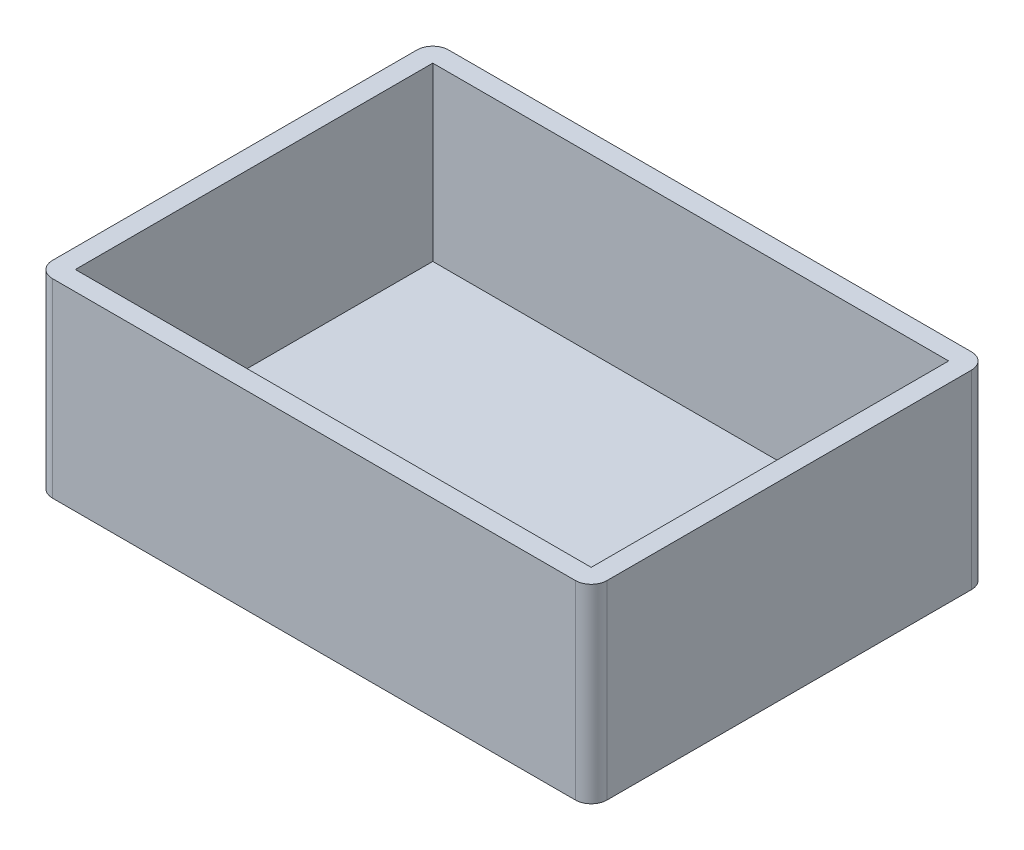
SolidWorks part; units mm, degrees
ref_plane "Front Plane" through (0, 0, 0) normal (0, 0, 1) x (1, 0, 0)
ref_plane "Top Plane" through (0, 0, 0) normal (0, 1, 0) x (1, 0, 0)
ref_plane "Right Plane" through (0, 0, 0) normal (1, 0, 0) x (0, 0, -1)
sketch "Sketch1" plane through (0, 0, 0) normal (0, 1, 0) x (1, 0, 0)
  line L0 (-155, 105) -> (155, 105) construction
  line L1 (162.8, -112.805) -> (-162.8, -112.805)
  line L2 (162.8, -112.805) -> (162.8, 112.805)
  line L3 (162.8, 112.805) -> (-162.8, 112.805)
  line L4 (-162.8, -112.805) -> (-162.8, 112.805)
  line L5 (162.8, -112.805) -> (-162.8, 112.805) construction
  line L6 (162.8, 112.805) -> (-162.8, -112.805) construction
  line L7 (175, -125) -> (-175, -125)
  line L8 (175, -125) -> (175, 125)
  line L9 (175, 125) -> (-175, 125)
  line L10 (-175, -125) -> (-175, 125)
  line L11 (175, -125) -> (-175, 125) construction
  line L12 (175, 125) -> (-175, -125) construction
  line L13 (155, 105) -> (-155, 105) construction
  line L14 (155, 105) -> (155, -105) construction
  line L15 (155, -105) -> (-155, -105) construction
  line L16 (-155, 105) -> (-155, -105) construction
  line L17 (155, 105) -> (-155, -105) construction
  line L18 (155, -105) -> (-155, 105) construction
  line L19 (-155, 105) -> (-155, -105) construction
  circle A0 centre (-155, 105) radius 2 construction
  circle A1 centre (155, 105) radius 2 construction
  circle A2 centre (155, -105) radius 2 construction
  circle A3 centre (-155, -105) radius 2 construction
  point P0 (0, 0)
  point P5 (0, 0)
  point P10 (0, 0)
  point P17 (0, 0)
  dimension "D7" = 4
  dimension "D1" = 250
  dimension "D2" = 350
  dimension "D3" = 225.61
  dimension "D4" = 325.6
  dimension "D5" = 310
  dimension "D10" = 310
  dimension "D11" = 210
  dimension "D8" = 2
  dimension "D9" = 2
extrude "Boss-Extrude1" add sketch "Sketch1" along normal blind 120
extrude "Boss-Extrude2" add sketch "Sketch1<2>" along normal blind 11.6 contours L4 L1 L2 L3 region at (0, 0, 0)
sketch "Sketch1<2>" plane through (0, 0, 0) normal (0, 1, 0) x (1, 0, 0) same geometry as "Sketch1"
fillet "Fillet1" radius 10 4 edges at (175, 60, 125) (-175, 60, 125) (-175, 60, -125) (175, 60, -125)
hole_wizard "M8 Clearance Hole1" positions "Sketch2" profile "Sketch3" hole size "M8" standard "ANSI Metric"
sketch "Sketch2" plane through (0, 0, 0) normal (0, -1, 0) x (-1, 0, 0)
  point P0 (155, -105)
  point P3 (-155, -105)
  point P6 (-155, 105)
  point P9 (155, 105)
sketch "Sketch3" plane through (-155, 0, 105) normal (1, 0, 0) x (0, 0, -1)
  line L0 (0, 0) -> (0, 10.5236)
  line L1 (0, 10.5236) -> (4.2, 8)
  line L2 (4.2, 8) -> (4.2, 0)
  line L5 (4.2, 0) -> (0, 0)
  line L10 (0, 10.5236) -> (-4.2, 8) construction
  line L11 (0, -6.35) -> (0, 107.95) construction
  dimension "Hole Dia." = 8.4
  dimension "Hole Depth" = 8
  dimension "Drill Angle" = 118
